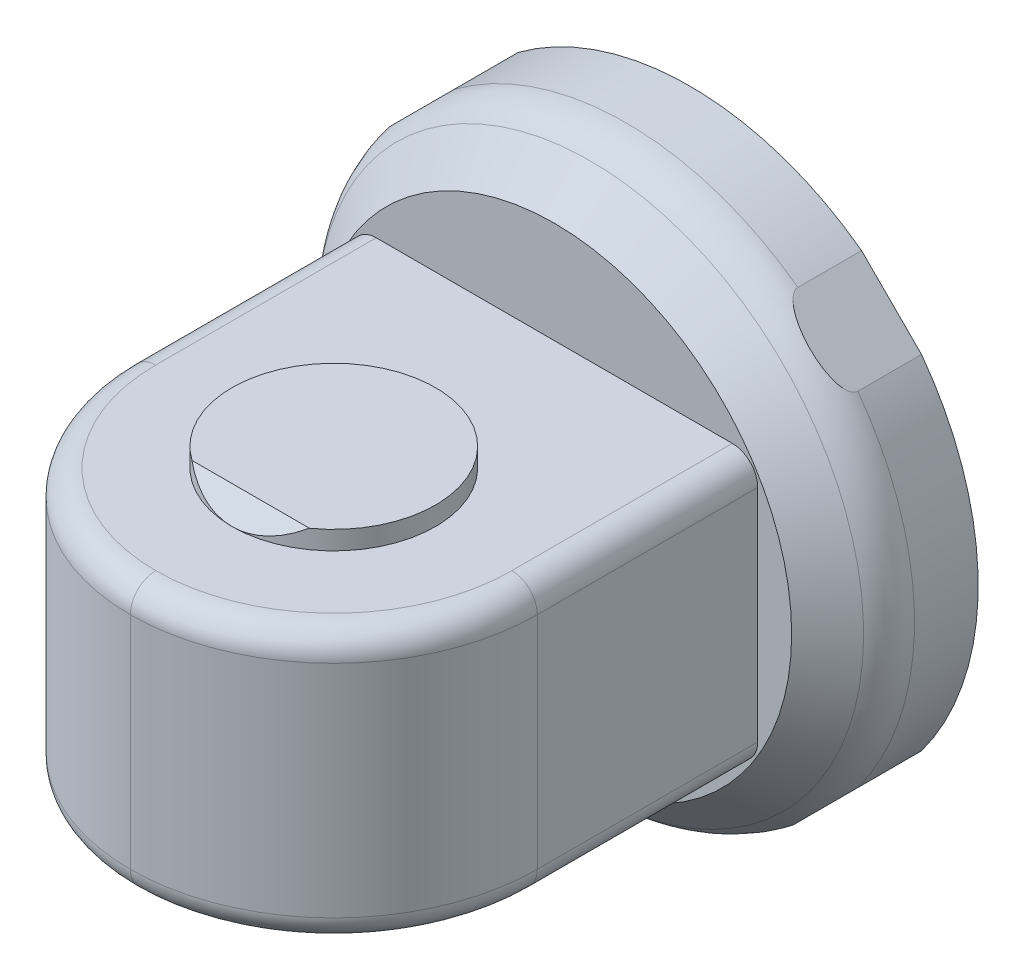
SolidWorks part; units mm, degrees
ref_plane "Front" through (0, 0, 0) normal (0, 0, 1) x (1, 0, 0)
ref_plane "Top" through (0, 0, 0) normal (0, 1, 0) x (1, 0, 0)
ref_plane "Right" through (0, 0, 0) normal (1, 0, 0) x (0, 0, -1)
sketch "Sketch1" plane through (0, 0, 0) normal (0, 0, 1) x (1, 0, 0)
  circle A0 centre (0, 0) radius 17
  dimension "D1" = 34
extrude "Extrude1" add sketch "Sketch1" along normal blind 8
sketch "Sketch2" plane through (0, 0, 8) normal (0, 0, 1) x (1, 0, 0)
  line L0 (0, 0) -> (0, 35.7997) construction
  line L1 (0, 0) -> (27.9831, 0) construction
  line L2 (12, 8) -> (12, -8)
  line L3 (12, 8) -> (-12, 8)
  line L4 (-12, 8) -> (-12, -8)
  line L5 (12, -8) -> (-12, -8)
  point P11 (-12, 0)
  point P12 (12, 0)
  dimension "D1" = 8
  dimension "D2" = 12
extrude "Extrude2" add sketch "Sketch2" along normal blind 25
fillet "Fillet1" radius 12 2 edges at (-12, 0, 33) (12, 0, 33)
chamfer "Chamfer1" distance 3 angle 45 1 edges at (17, 0, 8)
fillet "Fillet2" radius 3 1 edges at (17, 0, 5)
sketch "Sketch3" plane through (0, 8, 0) normal (0, 1, 0) x (1, 0, 0)
  circle A0 centre (0, -21) radius 6
  arc A1 (-12, -21) -> (0, -33) centre (0, -21) ccw construction
  dimension "D1" = 12
extrude "Extrude3" add sketch "Sketch3" along normal blind 1.1 and the other way blind 17.1
sketch "Sketch4" plane through (-12, 0, 0) normal (-1, 0, 0) x (0, 0, 1)
  line L0 (27, -8) -> (27, -9.1)
  line L1 (27, -9.1) -> (25.9, -9.1)
  line L2 (25.9, -9.1) -> (27, -8)
  line L3 (21, -8) -> (33, -8) construction
  line L4 (15, -9.1) -> (27, -9.1) construction
  line L5 (0, 0) -> (46.1177, 0) construction
  line L6 (25.9, 9.1) -> (27, 8)
  line L7 (27, 9.1) -> (25.9, 9.1)
  line L8 (27, 8) -> (27, 9.1)
  dimension "D1" = 45
extrude "Cut-Extrude1" cut sketch "Sketch4" against normal through all
fillet "Fillet3" radius 1.5 8 edges at (-12, 8, 14.2889) (-8.4853, 8, 29.4853) (12, 8, 14.2889) (12, -8, 14.2889) (-12, -8, 14.2889) (-8.4853, -8, 29.4853) (8.4853, 8, 29.4853) (8.4853, -8, 29.4853)
sketch "Sketch5" plane through (0, 0, 0) normal (0, 0, -1) x (-1, 0, 0)
  line L0 (0, 0) -> (0, 31.1729) construction
  line L1 (0, 0) -> (28.2922, 0) construction
  line L2 (-13.6579, 10.1224) -> (-10.1224, 13.6579)
  line L3 (13.6579, 10.1224) -> (10.1224, 13.6579)
  line L4 (13.6579, -10.1224) -> (10.1224, -13.6579)
  line L5 (-13.6579, -10.1224) -> (-10.1224, -13.6579)
  arc A1 (10.1224, 13.6579) -> (13.6579, 10.1224) centre (0, 0) cw
  arc A2 (-10.1224, 13.6579) -> (-13.6579, 10.1224) centre (0, 0) ccw
  arc A3 (10.1224, -13.6579) -> (13.6579, -10.1224) centre (0, 0) ccw
  arc A4 (-10.1224, -13.6579) -> (-13.6579, -10.1224) centre (0, 0) cw
  dimension "D1" = 45
  dimension "D2" = 5
extrude "Cut-Extrude2" cut sketch "Sketch5" against normal through all
